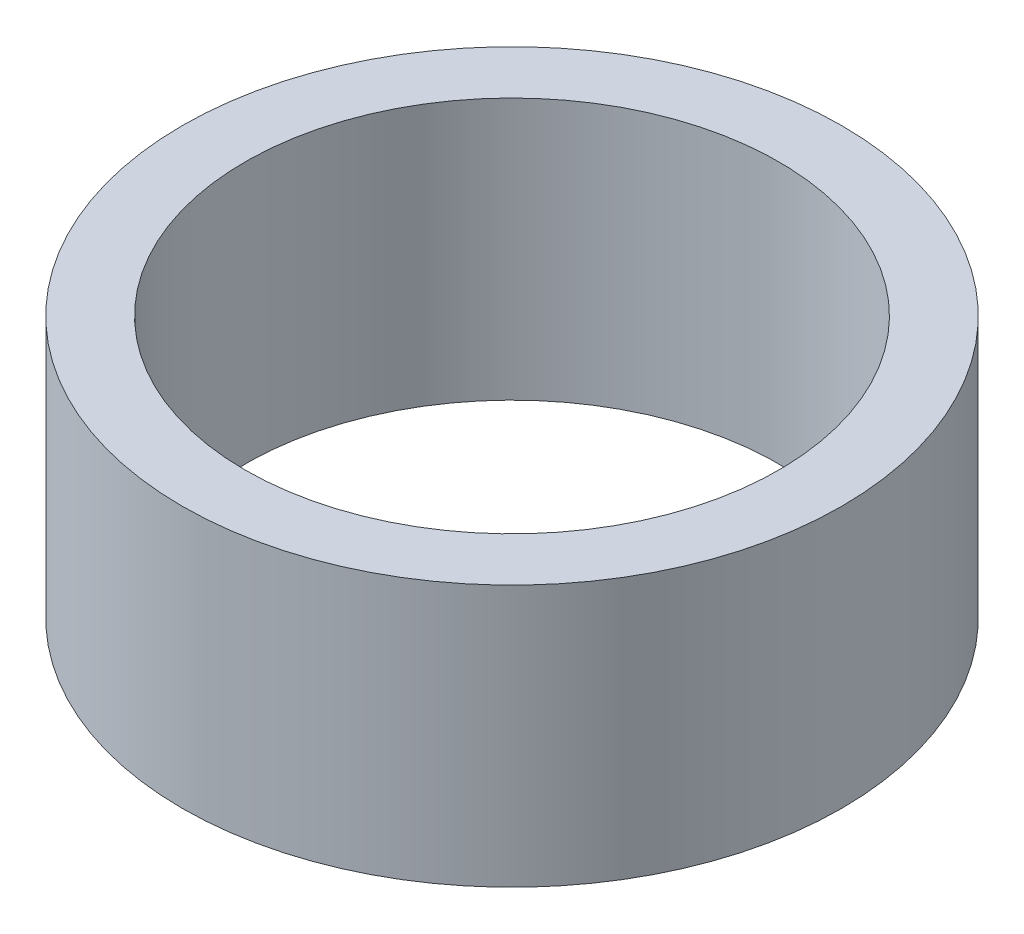
SolidWorks part; units mm, degrees
ref_plane "Front Plane" through (0, 0, 0) normal (0, 0, 1) x (1, 0, 0)
ref_plane "Top Plane" through (0, 0, 0) normal (0, 1, 0) x (1, 0, 0)
ref_plane "Right Plane" through (0, 0, 0) normal (1, 0, 0) x (0, 0, -1)
sketch "Sketch1" plane through (0, 0, 0) normal (0, 1, 0) x (1, 0, 0)
  circle A0 centre (0, 0) radius 2.55
  circle A1 centre (0, 0) radius 3.15
  dimension "D1" = 5.1
  dimension "D2" = 6.3
extrude "Boss-Extrude1" add sketch "Sketch1" along normal blind 2.5
